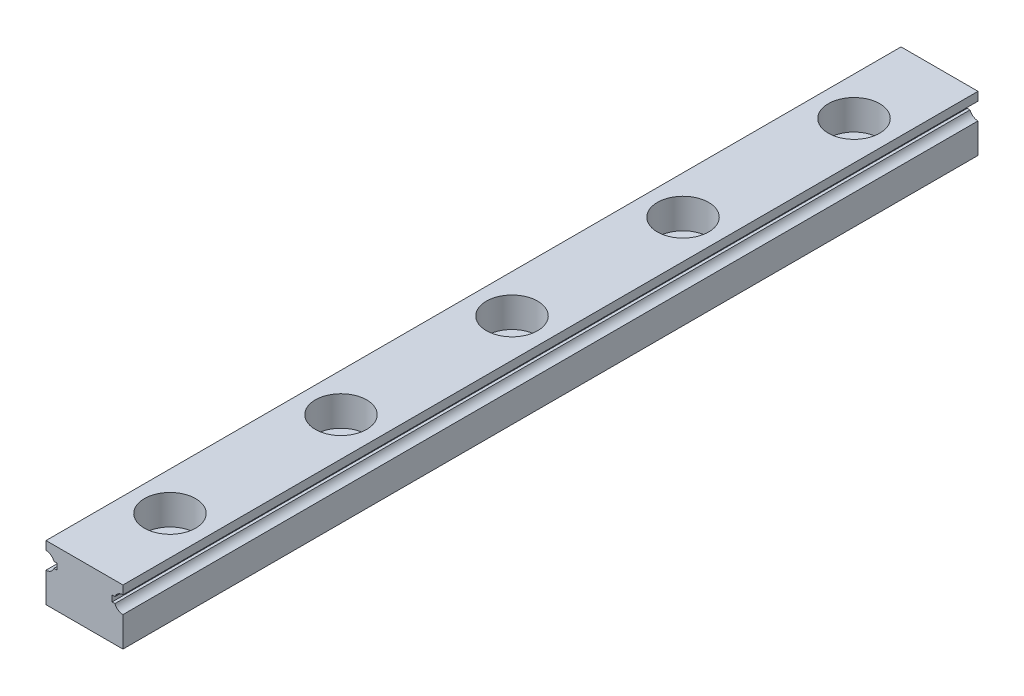
SolidWorks part; units mm, degrees
ref_plane "Спереди" through (0, 0, 0) normal (0, 0, 1) x (1, 0, 0)
ref_plane "Сверху" through (0, 0, 0) normal (0, 1, 0) x (1, 0, 0)
ref_plane "Справа" through (0, 0, 0) normal (1, 0, 0) x (0, 0, -1)
sketch "Sketch1" plane through (0, 0, 0) normal (0, 0, 1) x (1, 0, 0)
  line L0 (0, 0) -> (0, 5.7299) construction
  line L1 (-4.5, -3.25) -> (4.5, -3.25)
  line L2 (-4.5, -3.25) -> (-4.5, 0.25)
  line L3 (-4.5, 3.25) -> (4.5, 3.25)
  line L4 (4.5, -3.25) -> (4.5, 0.25)
  line L5 (-4.5, -3.25) -> (4.5, 3.25) construction
  line L6 (-4.5, 3.25) -> (4.5, -3.25) construction
  line L7 (-4.5, 2.25) -> (-4.5, 3.25)
  line L8 (-3.564, 0.898) -> (-3.2351, 0.898)
  line L9 (3.564, 0.898) -> (3.2351, 0.898)
  line L10 (-3.564, 1.602) -> (-3.2351, 1.602)
  line L11 (-3.2351, 0.898) -> (-3.2351, 1.602)
  line L12 (3.2351, 0.898) -> (3.2351, 1.602)
  line L13 (3.564, 1.602) -> (3.2351, 1.602)
  line L14 (4.5, 2.25) -> (4.5, 3.25)
  arc A0 (-3.564, 1.602) -> (-4.5, 2.25) centre (-4.5, 1.25) ccw
  arc A1 (-4.5, 0.25) -> (-3.564, 0.898) centre (-4.5, 1.25) ccw
  arc A2 (4.5, 0.25) -> (3.564, 0.898) centre (4.5, 1.25) cw
  arc A3 (3.564, 1.602) -> (4.5, 2.25) centre (4.5, 1.25) cw
  point P0 (0, 0)
  dimension "D3" = 1
  dimension "D1" = 9
  dimension "D2" = 6.5
  dimension "D4" = 2
extrude "Extrude1" add sketch "Sketch1" along normal blind 100
sketch "Sketch2" plane through (0, 3.25, 0) normal (0, 1, 0) x (1, 0, 0)
  line L0 (4.5, 0) -> (-4.5, 0) construction
  circle A0 centre (0, -10) radius 1.75
  circle A1 centre (0, -10) radius 3
  dimension "D1" = 3.5
  dimension "D2" = 6
  dimension "D3" = 10
extrude "Extrude2" cut sketch "Sketch2" against normal blind 3.5 contours A1
extrude "Extrude3" cut sketch "Sketch" against normal through all contours A0
sketch "Sketch" plane through (0, 3.25, 0) normal (0, 1, 0) x (1, 0, 0) same geometry as "Sketch2"
pattern_linear "LPattern1" count 13 spacing 20 along (0, 0, 1) of "Extrude2", "Extrude3"
